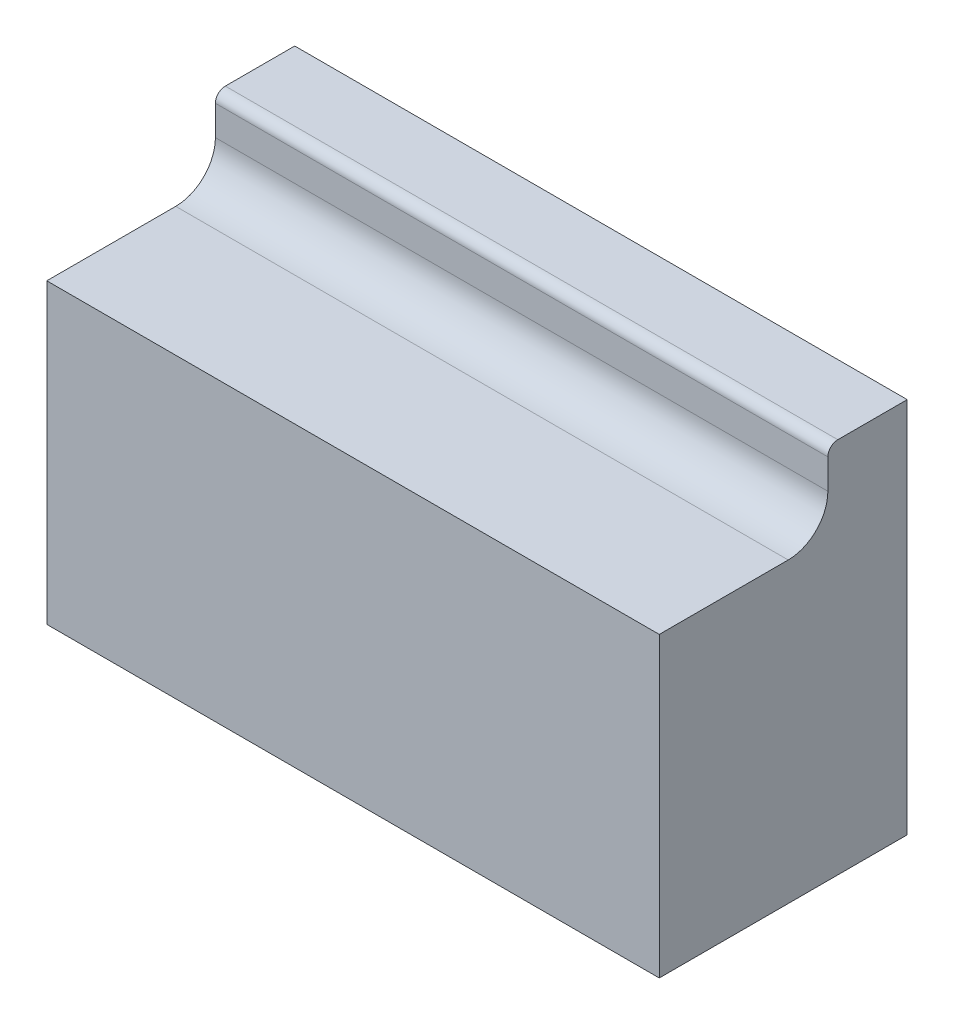
SolidWorks part; units mm, degrees
material "K110"
ref_plane "Front Plane" through (0, 0, 0) normal (0, 0, 1) x (1, 0, 0)
ref_plane "Top Plane" through (0, 0, 0) normal (0, 1, 0) x (1, 0, 0)
ref_plane "Right Plane" through (0, 0, 0) normal (1, 0, 0) x (0, 0, -1)
sketch "Sketch1" plane through (0, 0, 0) normal (0, 0, 1) x (1, 0, 0)
  line L1 (5.7154, -38) -> (67.4654, -38)
  line L2 (5.7154, -38) -> (5.7154, 0)
  line L3 (5.7154, 0) -> (67.4654, 0)
  line L4 (67.4654, -38) -> (67.4654, 0)
  dimension "D1" = 38
  dimension "D2" = 61.75
extrude "Boss-Extrude1" add sketch "Sketch1" along normal mid plane 25
sketch "Sketch2" plane through (67.4654, 0, 0) normal (1, 0, 0) x (0, 0, -1)
  line L0 (-12.5, -8) -> (0.5, -8)
  line L1 (-12.5, -38) -> (-12.5, 0) construction
  line L2 (4.5, -4) -> (4.5, 0)
  line L3 (-12.5, 0) -> (12.5, 0) construction
  line L4 (4.5, 0) -> (-12.5, 0)
  line L5 (-12.5, 0) -> (-12.5, -8)
  line L6 (0.5, -8) -> (0.5, -6) construction
  line L7 (1.809, -8) -> (-53.191, -8) construction
  arc A0 (0.5, -8) -> (4.5, -4) centre (0.5, -4) ccw
  arc A1 (0.5, -8) -> (2.5, -7.4641) centre (0.5, -4) ccw construction
  point P9 (4.5, -8)
extrude "Cut-Extrude1" cut sketch "Sketch2" against normal up to next
fillet "Fillet1" radius 1 1 edges at (36.5904, 0, -4.5)
